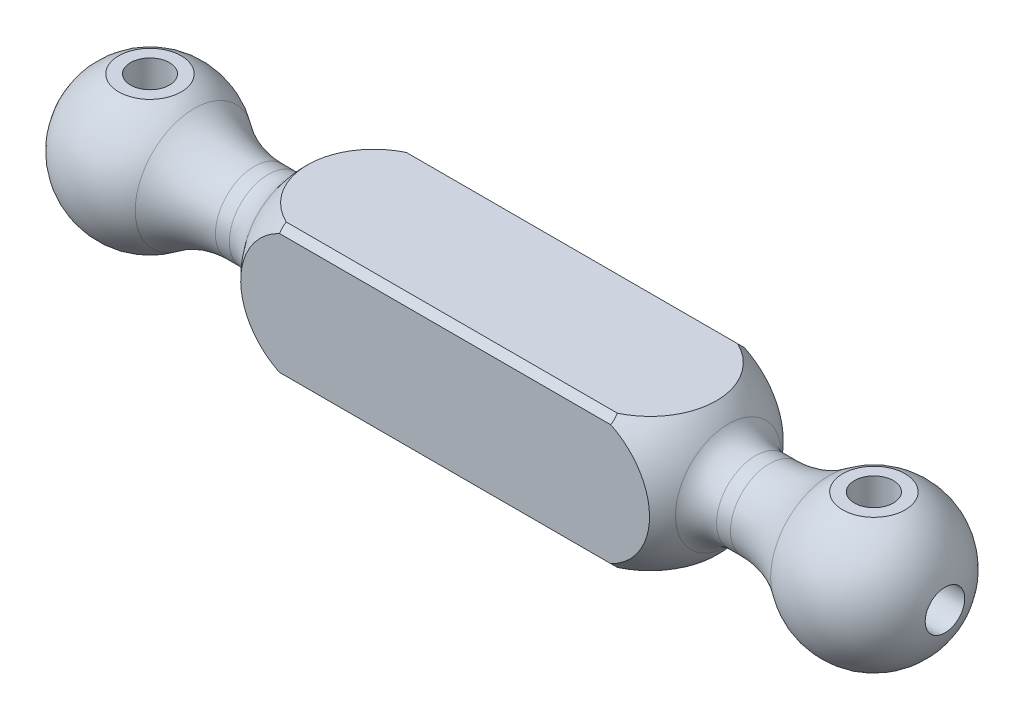
SolidWorks part; units mm, degrees
material "ABS"
ref_plane "Front Plane" through (0, 0, 0) normal (0, 0, 1) x (1, 0, 0)
ref_plane "Top Plane" through (0, 0, 0) normal (0, 1, 0) x (1, 0, 0)
ref_plane "Right Plane" through (0, 0, 0) normal (1, 0, 0) x (0, 0, -1)
sketch "Sketch1" plane through (0, 0, 0) normal (0, 0, 1) x (1, 0, 0)
  line L0 (-51.0327, 0) -> (98.3814, 0) construction
  line L1 (-60.0318, 6) -> (60.0318, 6)
  line L2 (-60.0318, 6) -> (-60.0318, -6)
  line L3 (-60.0318, -6) -> (60.0318, -6)
  line L4 (60.0318, 6) -> (60.0318, -6)
  line L5 (-60.0318, 6) -> (60.0318, -6) construction
  line L6 (-60.0318, -6) -> (60.0318, 6) construction
  line L7 (-29.875, 3.5) -> (-21.875, 3.5)
  line L8 (-29.875, 3.5) -> (-29.875, -3.5)
  line L9 (-29.875, -3.5) -> (-21.875, -3.5)
  line L10 (-21.875, 3.5) -> (-21.875, -3.5)
  line L11 (-29.875, 3.5) -> (-21.875, -3.5) construction
  line L12 (-29.875, -3.5) -> (-21.875, 3.5) construction
  line L13 (29.875, 3.5) -> (21.875, 3.5)
  line L14 (29.875, 3.5) -> (29.875, -3.5)
  line L15 (29.875, -3.5) -> (21.875, -3.5)
  line L16 (21.875, 3.5) -> (21.875, -3.5)
  line L17 (29.875, 3.5) -> (21.875, -3.5) construction
  line L18 (29.875, -3.5) -> (21.875, 3.5) construction
  line L19 (-41.1469, 0) -> (49.3696, 0)
  circle A0 centre (-32.5, 0) radius 6.625
  circle A1 centre (32.5, 0) radius 6.625
  point P0 (0, 0)
  point P10 (25.875, 0)
  point P12 (-25.875, 0)
  dimension "D2" = 13.25
  dimension "D3" = 13.25
  dimension "D1" = 12
  dimension "D4" = 65
  dimension "D5" = 32.5
  dimension "D6" = 7
  dimension "D7" = 8
  dimension "D8" = 7
  dimension "D9" = 8
revolve "Revolve2" add sketch "Sketch1" angle 360 about L0 region at (-32.5, 6.251, 0) region at (-33.5725, 2.9335, 0) region at (32.5, 6.251, 0) region at (33.5725, 2.9335, 0) region at (-28.0245, 1.672, 0) region at (-24.0463, 1.8163, 0) region at (24.0463, 1.8163, 0) region at (28.0245, 1.672, 0)
extrude "Cut-Extrude1" cut sketch "Sketch1<4>" against normal through all both and the other way through all contours L3 A0 | L1 A0 | L3 A1 | L1 A1 region at (-32.5, 6.251, 0) region at (-32.5, -6.251, 0) region at (32.5, 6.251, 0) region at (32.5, -6.251, 0)
sketch "Sketch1<4>" plane through (0, 0, 0) normal (0, 0, 1) x (1, 0, 0) same geometry as "Sketch1"
sketch "Sketch2" plane through (0, 0, 0) normal (0, 0, 1) x (1, 0, 0)
  line L0 (21.875, 3.5) -> (21.875, -3.5) construction
  line L1 (-21.875, -6) -> (21.875, -6)
  line L2 (-21.875, -6) -> (-21.875, 6)
  line L3 (-21.875, 6) -> (21.875, 6)
  line L4 (21.875, -6) -> (21.875, 6)
  line L5 (-21.875, -3.5) -> (-21.875, 3.5) construction
  dimension "D1" = 6
  dimension "D2" = 12
extrude "Boss-Extrude1" add sketch "Sketch2" along normal blind 6 and the other way blind 6
fillet "Fillet1" radius 9 2 edges at (26.875, 0, 3.5) (-26.875, 0, 3.5)
sketch "Sketch3" plane through (0, 0, 0) normal (0, 1, 0) x (1, 0, 0)
  line L1 (-21.875, 3.5) -> (-21.875, -3.5) construction
  line L2 (-21.875, 6) -> (21.875, 6) construction
  line L3 (-21.875, 6.5) -> (-21.875, 14.5)
  line L4 (-21.875, 14.5) -> (-12.1282, 14.5)
  line L5 (-12.1282, 14.5) -> (-12.1282, -0.5)
  line L6 (21.875, 6) -> (21.875, -6) construction
  line L7 (12.1282, -0.5) -> (12.1282, 14.5)
  line L8 (12.1282, 14.5) -> (21.875, 14.5)
  line L9 (21.875, 14.5) -> (21.875, 6.5)
  line L10 (-48.4942, 0) -> (55.786, 0) construction
  circle A0 centre (-21.875, 6.5) radius 3
  circle A1 centre (-12.1282, -0.5) radius 9
  circle A2 centre (12.1282, -0.5) radius 9
  circle A3 centre (21.875, 6.5) radius 3
  dimension "D2" = 6
  dimension "D3" = 18
  dimension "D6" = 6
  dimension "D7" = 18
  dimension "D1" = 6.5
  dimension "D4" = 6.5
  dimension "D5" = 15
  dimension "D8" = 15
revolve "Cut-Revolve1" cut sketch "Sketch3" angle 360 about L10 region at (-16.948, 0, -11.1435) region at (-19.8137, 0, -8.5613) region at (16.948, 0, -11.1435) region at (19.2812, 0, -7.8306)
sketch "Sketch4" plane through (0, -6, 0) normal (0, -1, 0) x (1, 0, 0)
  circle A0 centre (-32.5, 0) radius 1.75
  circle A1 centre (32.5, 0) radius 1.75
  circle A2 centre (-32.5, 0) radius 2.809 construction
  circle A3 centre (32.5, 0) radius 2.809 construction
  dimension "D1" = 3.5
  dimension "D2" = 3.5
extrude "Cut-Extrude2" cut sketch "Sketch4" against normal through all
sketch "Sketch6" plane through (0, 0, 0) normal (0, 0, 1) x (1, 0, 0)
  point P0 (-32.5, 0)
  point P1 (32.5, 0)
  dimension "D1" = 32.5
  dimension "D2" = 32.5
sketch "Sketch7" plane through (0, 0, 0) normal (1, 0, 0) x (0, 0, -1)
  circle A0 centre (0, 0) radius 1.775
  dimension "D1" = 3.55
extrude "Cut-Extrude3" cut sketch "Sketch7" against normal through all both and the other way through all
chamfer "Chamfer1" distance 0.6 angle 45 4 edges at (0, -6, 6) (0, -6, -6) (0, 6, -6) (0, 6, 6)
equation "\"D5@Sketch1\"=\"D4@Sketch1\"/2"
equation "\"D2@Sketch4\"=\"D1@Sketch4\""
